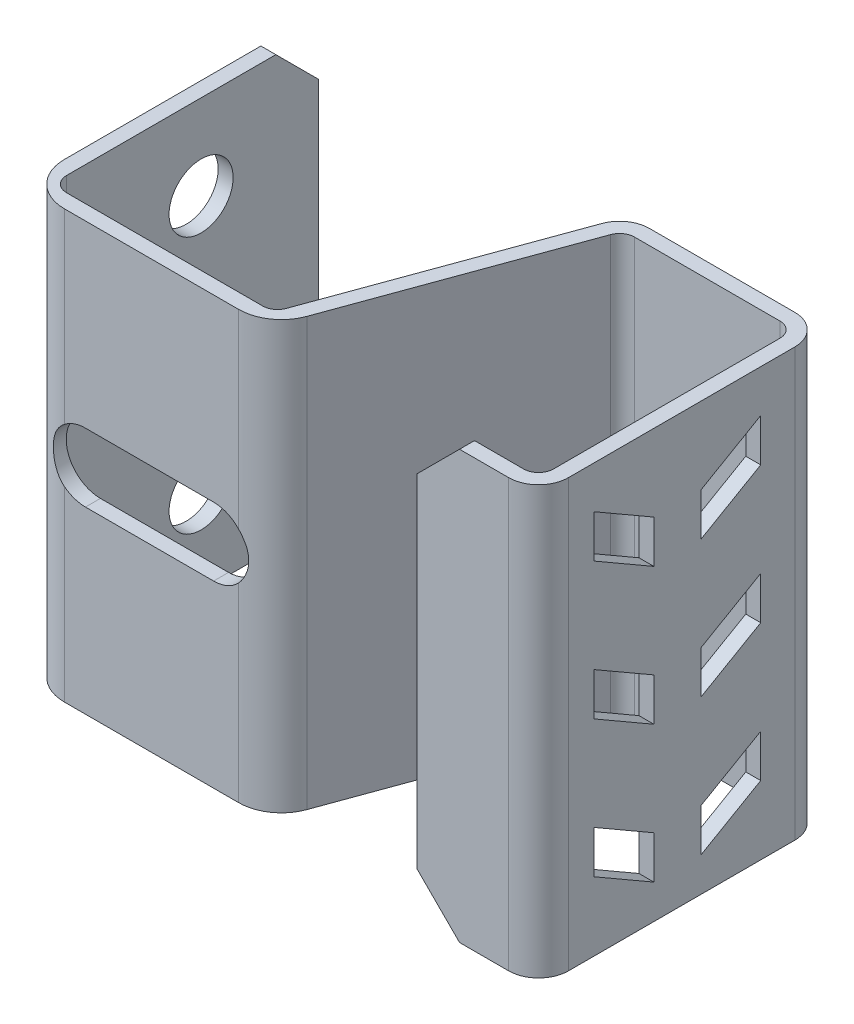
SolidWorks part; units mm, degrees
ref_plane "Front Plane" through (0, 0, 0) normal (0, 0, 1) x (1, 0, 0)
ref_plane "Top Plane" through (0, 0, 0) normal (0, 1, 0) x (1, 0, 0)
ref_plane "Right Plane" through (0, 0, 0) normal (1, 0, 0) x (0, 0, -1)
sketch "Sketch1" plane through (0, 0, 0) normal (0, 1, 0) x (1, 0, 0)
  line L0 (0, 0) -> (21.5, 0)
  line L1 (25, 3.5) -> (25, 56.5)
  line L2 (21.5, 60) -> (-12.5493, 60)
  line L3 (-15.8382, 57.6971) -> (-37.2022, -1)
  line L4 (-37.2022, -1) -> (-95, -1)
  line L5 (-95, -1) -> (-95, 65)
  line L6 (0, -3.5) -> (21.5, -3.5)
  line L7 (28.5, 3.5) -> (28.5, 56.5)
  line L8 (21.5, 63.5) -> (-12.5493, 63.5)
  line L9 (-19.1271, 58.8941) -> (-38.8147, 4.8029)
  line L10 (-42.1036, 2.5) -> (-88, 2.5)
  line L11 (-91.5, 6) -> (-91.5, 65)
  line L12 (-19.1271, 58.8941) -> (-39.6529, 2.5) construction
  line L13 (-39.6529, 2.5) -> (-91.5, 2.5) construction
  line L14 (-91.5, 2.5) -> (-91.5, 65) construction
  line L15 (-95, 65) -> (-91.5, 65)
  line L16 (0, -3.5) -> (0, 0)
  arc A0 (21.5, 0) -> (25, 3.5) centre (21.5, 3.5) ccw
  arc A1 (-12.5493, 60) -> (-15.8382, 57.6971) centre (-12.5493, 56.5) ccw
  arc A2 (25, 56.5) -> (21.5, 60) centre (21.5, 56.5) ccw
  arc A3 (21.5, -3.5) -> (28.5, 3.5) centre (21.5, 3.5) ccw
  arc A4 (28.5, 56.5) -> (21.5, 63.5) centre (21.5, 56.5) ccw
  arc A5 (-12.5493, 63.5) -> (-19.1271, 58.8941) centre (-12.5493, 56.5) ccw
  arc A6 (-38.8147, 4.8029) -> (-42.1036, 2.5) centre (-42.1036, 6) cw
  arc A7 (-88, 2.5) -> (-91.5, 6) centre (-88, 6) cw
  point P10 (25, 0)
  point P13 (-15, 60)
  point P16 (25, 60)
  dimension "D8" = 3.5
  dimension "D10" = 3.5
  dimension "D11" = 3.5
  dimension "D1" = 25
  dimension "D2" = 60
  dimension "D3" = 40
  dimension "D4" = 110
  dimension "D5" = 1
  dimension "D6" = 120
  dimension "D7" = 66
  dimension "D9" = 3.5
extrude "Boss-Extrude2" add sketch "Sketch1" along normal blind 100
chamfer "Chamfer1" distance 10 angle 45 4 edges at (0, 100, 1.75) (0, 0, 1.75) (-93.25, 0, -65) (-93.25, 100, -65)
sketch "Sketch2" plane through (-95, 0, 0) normal (-1, 0, 0) x (0, 0, 1)
  line L0 (3.5, 90) -> (3.5, 10) construction
  line L1 (-69.7146, 50) -> (76.7146, 50) construction
  circle A0 centre (-37.5, 19.9) radius 7.5
  circle A1 centre (-37.5, 80.1) radius 7.5
  point P8 (3.5, 50)
  dimension "D1" = 15
  dimension "D2" = 60.2
  dimension "D3" = 41
  dimension "D4" = 30.1
extrude "Cut-Extrude1" cut sketch "Sketch2" against normal up to surface (3.5 mm away) up to face at (-91.5, 50, -42)
sketch "Sketch3" plane through (0, 0, -2.5) normal (0, 0, -1) x (-1, 0, 0)
  line L0 (50.0691, 50) -> (80.0691, 50) construction
  line L1 (50.0691, 58) -> (80.0691, 58)
  line L2 (50.0691, 42) -> (80.0691, 42)
  line L4 (42.1036, 0) -> (88, 0) construction
  line L5 (-28.5, 100) -> (-28.5, 0) construction
  arc A0 (50.0691, 58) -> (50.0691, 42) centre (50.0691, 50) ccw
  arc A1 (80.0691, 42) -> (80.0691, 58) centre (80.0691, 50) ccw
  point P2 (65.0691, 50)
  dimension "D2" = 8
  dimension "D3" = 78.5691
  dimension "D1" = 30
  dimension "D4" = 50
extrude "Cut-Extrude2" cut sketch "Sketch3" against normal up to surface (3.5 mm away) up to face at (-66.1011, 50, 1)
sketch "Sketch4" plane through (28.5, 0, 0) normal (1, 0, 0) x (0, 0, -1)
  line L1 (48.5, 26.0829) -> (48.5, 16.0829)
  line L5 (34.5, 18) -> (34.5, 8)
  line L10 (34.5, 8) -> (48.5, 16.0829)
  line L11 (48.5, 26.0829) -> (34.5, 18)
  line L12 (23.5, 18) -> (23.5, 8)
  line L16 (-3.5, 100) -> (-3.5, 0) construction
  line L17 (23.5, 18) -> (9.5, 26.0829)
  line L18 (9.5, 26.0829) -> (9.5, 16.0829)
  line L19 (9.5, 16.0829) -> (23.5, 8)
  line L20 (3.5, 0) -> (56.5, 0) construction
  line L21 (48.5, 58.0829) -> (48.5, 48.0829)
  line L22 (48.5, 58.0829) -> (34.5, 50)
  line L23 (34.5, 40) -> (48.5, 48.0829)
  line L24 (34.5, 50) -> (34.5, 40)
  line L25 (23.5, 50) -> (23.5, 40)
  line L26 (9.5, 48.0829) -> (23.5, 40)
  line L27 (23.5, 50) -> (9.5, 58.0829)
  line L28 (9.5, 58.0829) -> (9.5, 48.0829)
  line L29 (48.5, 90.0829) -> (48.5, 80.0829)
  line L30 (48.5, 90.0829) -> (34.5, 82)
  line L31 (34.5, 72) -> (48.5, 80.0829)
  line L32 (34.5, 82) -> (34.5, 72)
  line L33 (23.5, 82) -> (23.5, 72)
  line L34 (9.5, 80.0829) -> (23.5, 72)
  line L35 (23.5, 82) -> (9.5, 90.0829)
  line L36 (9.5, 90.0829) -> (9.5, 80.0829)
  dimension "D1" = 10
  dimension "D2" = 14
  dimension "D3" = 14
  dimension "D4" = 11
  dimension "D5" = 8
  dimension "D6" = 60
  dimension "D7" = 60
  dimension "D8" = 13
  dimension "D9" = 3
  dimension "D10" = 22
extrude "Cut-Extrude3" cut sketch "Sketch4" against normal blind 10
fillet "Fillet1" radius 10 2 edges at (-95, 50, 1) (-37.2022, 50, 1)
